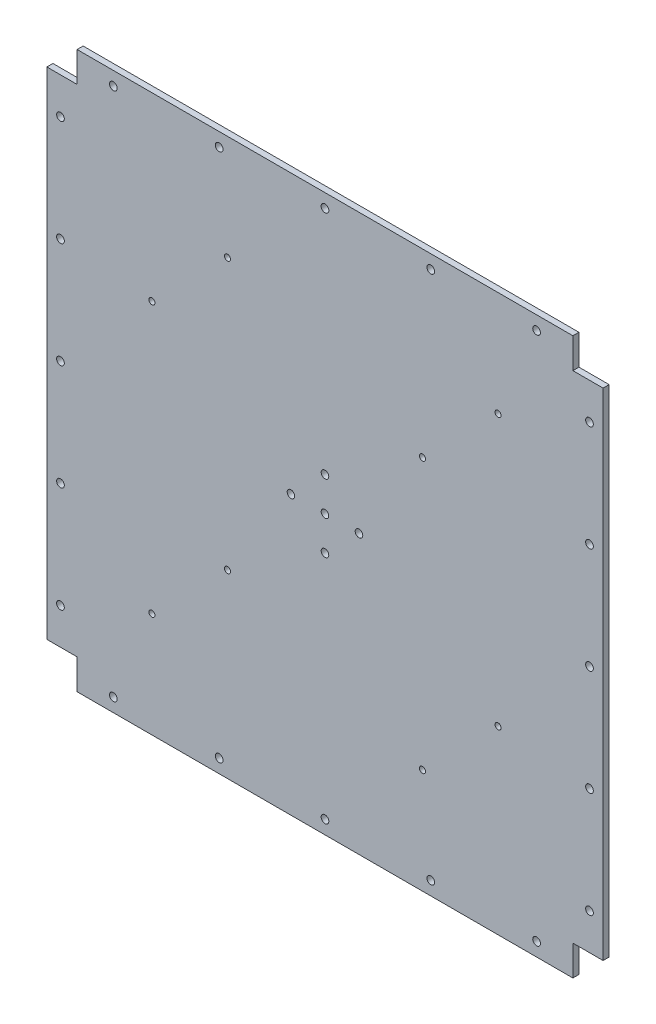
SolidWorks part; units mm, degrees
ref_plane "前视基准面" through (0, 0, 0) normal (0, 0, 1) x (1, 0, 0)
ref_plane "上视基准面" through (0, 0, 0) normal (0, 1, 0) x (1, 0, 0)
ref_plane "右视基准面" through (0, 0, 0) normal (1, 0, 0) x (0, 0, -1)
sketch "草图1" plane through (0, 0, 0) normal (0, 0, 1) x (1, 0, 0)
  line L1 (184, -184) -> (-184, -184)
  line L2 (184, -184) -> (184, 184)
  line L3 (184, 184) -> (-184, 184)
  line L4 (-184, -184) -> (-184, 184)
  line L5 (184, -184) -> (-184, 184) construction
  line L6 (184, 184) -> (-184, -184) construction
  point P0 (0, 0)
  dimension "D1" = 368
  dimension "D2" = 368
extrude "凸台-拉伸1" add sketch "草图1" along normal blind 4
sketch "草图3" plane through (0, 0, 4) normal (0, 0, 1) x (1, 0, 0)
  line L0 (0, -184) -> (0, -175) construction
  line L1 (-184, -184) -> (184, -184) construction
  circle A0 centre (0, -175) radius 2.55
  circle A1 centre (70, -175) radius 2.55
  circle A2 centre (140, -175) radius 2.55
  circle A3 centre (-70, -175) radius 2.55
  circle A4 centre (-140, -175) radius 2.55
  circle A30 centre (-175, 140) radius 2.55
  circle A31 centre (-175, 70) radius 2.55
  circle A32 centre (-175, -70) radius 2.55
  circle A33 centre (-175, -140) radius 2.55
  circle A34 centre (-175, 0) radius 2.55
  circle A35 centre (140, 175) radius 2.55
  circle A36 centre (70, 175) radius 2.55
  circle A37 centre (-70, 175) radius 2.55
  circle A38 centre (-140, 175) radius 2.55
  circle A39 centre (0, 175) radius 2.55
  circle A40 centre (175, -140) radius 2.55
  circle A41 centre (175, -70) radius 2.55
  circle A42 centre (175, 70) radius 2.55
  circle A43 centre (175, 140) radius 2.55
  circle A44 centre (175, 0) radius 2.55
  point P47 (10, -10)
  point P78 (0, 0)
  dimension "D1" = 5.1
  dimension "D2" = 9
  dimension "D3" = 3
  dimension "D4" = 3
  dimension "D6" = 4
extrude "切除-拉伸2" cut sketch "草图3" against normal through all
sketch "草图4" plane through (0, 0, 4) normal (0, 0, 1) x (1, 0, 0)
  line L0 (-164, 184) -> (-164, 164)
  line L1 (-184, -184) -> (-164, -184)
  line L2 (-184, -184) -> (-184, -164)
  line L3 (-184, -164) -> (-164, -164)
  line L4 (-164, -184) -> (-164, -164)
  line L5 (-184, 164) -> (-164, 164)
  line L6 (-184, 184) -> (-164, 184)
  line L7 (-184, 184) -> (-184, 164)
  line L8 (184, 164) -> (164, 164)
  line L9 (164, 184) -> (164, 164)
  line L10 (184, 184) -> (184, 164)
  line L11 (184, 184) -> (164, 184)
  line L12 (164, -184) -> (164, -164)
  line L13 (184, -164) -> (164, -164)
  line L14 (184, -184) -> (164, -184)
  line L15 (184, -184) -> (184, -164)
  point P20 (0, 0)
  dimension "D1" = 20
  dimension "D2" = 20
  dimension "D3" = 4
extrude "切除-拉伸3" cut sketch "草图4" against normal through all contours L0 L5 L7 L6 | L8 L9 L11 L10 | L12 L13 L15 L14 | L2 L1 L4 L3
sketch "草图5" plane through (0, 0, 4) normal (0, 0, 1) x (1, 0, 0)
  line L0 (-184, 0) -> (184, 0) construction
  line L1 (-184, 164) -> (-184, -164) construction
  line L2 (-184, 164) -> (-184, -164) construction
  line L3 (0, 184) -> (0, -184) construction
  line L4 (164, 184) -> (-164, 184) construction
  line L5 (-164, -184) -> (164, -184) construction
  line L6 (-10, 0) -> (-22.5, 0) construction
  line L11 (10, -10) -> (-10, 10) construction
  line L12 (10, 10) -> (-10, -10) construction
  line L13 (0, -10) -> (0, -22.5) construction
  line L14 (10, 0) -> (22.5, 0) construction
  line L15 (0, 10) -> (0, 22.5) construction
  line L16 (-173.9781, 173.9781) -> (0, 0) construction
  line L17 (-184, 0) -> (0, 184) construction
  line L19 (-14.489, 14.489) -> (-159.489, 14.489) construction
  line L20 (-14.489, 14.489) -> (-14.489, 159.489) construction
  line L21 (-14.489, 159.489) -> (-159.489, 159.489) construction
  line L22 (-159.489, 14.489) -> (-159.489, 159.489) construction
  line L23 (-14.489, 14.489) -> (-159.489, 159.489) construction
  line L24 (-14.489, 159.489) -> (-159.489, 14.489) construction
  circle A0 centre (0, 22.5) radius 2.5
  circle A1 centre (22.5, 0) radius 2.5
  circle A2 centre (-22.5, 0) radius 2.5
  circle A3 centre (0, -22.5) radius 2.5
  circle A4 centre (0, 0) radius 2.5
  point P4 (-86.989, 86.989)
  point P12 (0, 0)
  dimension "D7" = 5
  dimension "D8" = 5
  dimension "D9" = 5
  dimension "D10" = 5
  dimension "D11" = 5
  dimension "D1" = 20
  dimension "D2" = 20
  dimension "D3" = 12.5
  dimension "D4" = 12.5
  dimension "D5" = 12.5
  dimension "D6" = 12.5
  dimension "D12" = 145
  dimension "D13" = 145
extrude "切除-拉伸6" cut sketch "草图5" against normal blind 10
sketch "草图6" plane through (0, 0, 0) normal (0, 0, -1) x (-1, 0, 0)
  circle A0 centre (114.5, 64.5) radius 2
  circle A1 centre (64.5, 114.5) radius 2
  circle A2 centre (114.5, -114.5) radius 2
  circle A3 centre (64.5, -64.5) radius 2
  circle A4 centre (-64.5, -114.5) radius 2
  circle A5 centre (-114.5, -64.5) radius 2
  circle A6 centre (-64.5, 64.5) radius 2
  circle A7 centre (-114.5, 114.5) radius 2
extrude "切除-拉伸7" cut sketch "草图6" against normal through all
